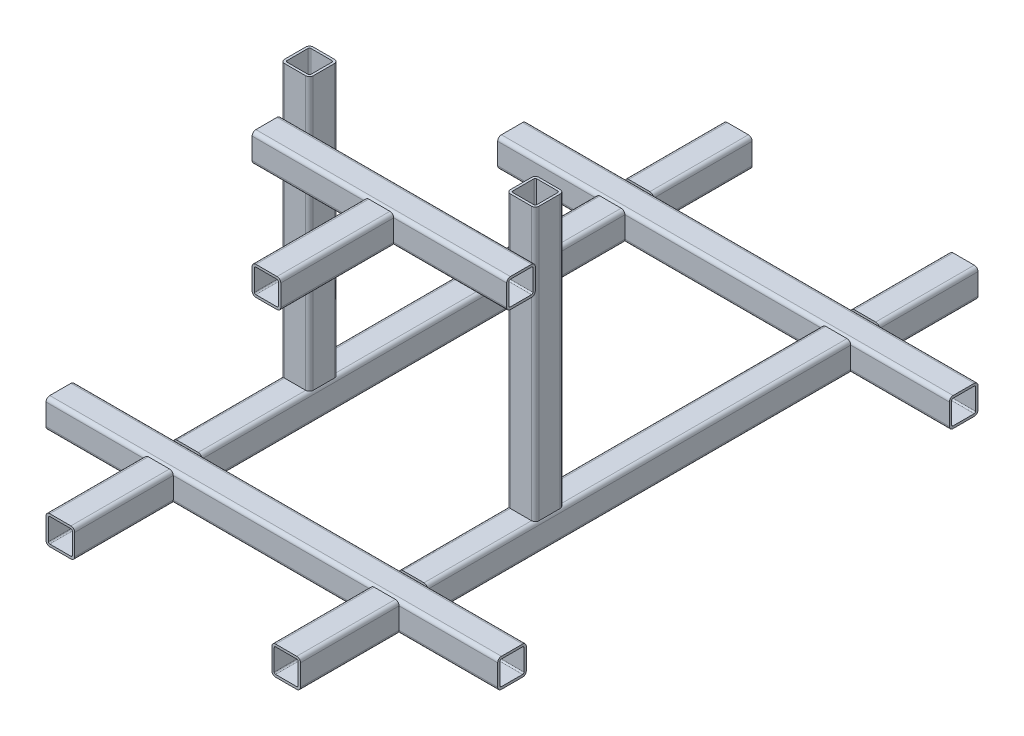
SolidWorks part; units mm, degrees
ref_plane "Front Plane" through (0, 0, 0) normal (0, 0, 1) x (1, 0, 0)
ref_plane "Top Plane" through (0, 0, 0) normal (0, 1, 0) x (1, 0, 0)
ref_plane "Right Plane" through (0, 0, 0) normal (1, 0, 0) x (0, 0, -1)
ref_plane "Bottom Face" through (0, 0, 0) normal (0, 1, 0) x (1, 0, 0)
ref_plane "Top Face" through (0, 38.1, 0) normal (0, 1, 0) x (1, 0, 0)
ref_plane "Mid Plane" through (0, 19.05, 0) normal (0, 1, 0) x (1, 0, 0)
ref_plane "Front Face" through (0, 0, 450) normal (0, 0, 1) x (1, 0, 0)
ref_plane "Back Face" through (0, 0, -450) normal (0, 0, 1) x (1, 0, 0)
ref_plane "Left Face" through (300, 0, 0) normal (1, 0, 0) x (0, 0, -1)
ref_plane "Right Face" through (-300, 0, 0) normal (1, 0, 0) x (0, 0, -1)
ref_plane "Divider Plane" through (0, 0, 100) normal (0, 0, 1) x (1, 0, 0)
ref_plane "Max Height Plane" through (0, 400, 0) normal (0, 1, 0) x (1, 0, 0)
ref_plane "Electronics Box Plane" through (0, 338.1, 0) normal (0, 1, 0) x (1, 0, 0)
sketch "Sketch2" plane through (300, 0, 0) normal (1, 0, 0) x (0, 0, -1)
  line L0 (275, 38.1) -> (-275, 38.1) construction
  line L5 (275, 0) -> (-275, 0) construction
  line L6 (0, 20.955) -> (0, -20.955) construction
  line L7 (-314.05, 38.1) -> (-285.95, 38.1)
  line L8 (-280.95, 33.1) -> (-280.95, 5)
  line L9 (-315.875, 33.1) -> (-315.875, 5)
  line L10 (-314.05, 3.175) -> (-285.95, 3.175)
  line L11 (-285.95, 0) -> (-314.05, 0)
  line L12 (-319.05, 5) -> (-319.05, 33.1)
  line L13 (-300, 38.1) -> (-300, 0) construction
  line L14 (-319.05, 19.05) -> (-280.95, 19.05) construction
  line L15 (-284.125, 5) -> (-284.125, 33.1)
  line L16 (-285.95, 34.925) -> (-314.05, 34.925)
  line L17 (-300, 34.925) -> (-300, 3.175) construction
  line L18 (-315.875, 19.05) -> (-284.125, 19.05) construction
  arc A0 (-285.95, 38.1) -> (-280.95, 33.1) centre (-285.95, 33.1) cw
  arc A1 (-280.95, 5) -> (-285.95, 0) centre (-285.95, 5) cw
  arc A2 (-314.05, 0) -> (-319.05, 5) centre (-314.05, 5) cw
  arc A3 (-319.05, 33.1) -> (-314.05, 38.1) centre (-314.05, 33.1) cw
  arc A4 (-315.875, 5) -> (-314.05, 3.175) centre (-314.05, 5) ccw
  arc A5 (-285.95, 3.175) -> (-284.125, 5) centre (-285.95, 5) ccw
  arc A6 (-284.125, 33.1) -> (-285.95, 34.925) centre (-285.95, 33.1) ccw
  arc A7 (-314.05, 34.925) -> (-315.875, 33.1) centre (-314.05, 33.1) ccw
  point P20 (-300, 19.05)
  point P39 (-300, 19.05)
  dimension "D1" = 5
  dimension "D2" = 300
  dimension "D3" = 3.175
extrude "Front Cross-Car Member" add sketch "Sketch2" against normal up to surface (600 mm away) up to plane "Right Face"
sketch "Sketch5" plane through (300, 0, 0) normal (1, 0, 0) x (0, 0, -1)
  line L0 (285.95, 38.1) -> (314.05, 38.1)
  line L1 (319.05, 33.1) -> (319.05, 5)
  line L2 (314.05, 0) -> (285.95, 0)
  line L3 (280.95, 5) -> (280.95, 33.1)
  line L4 (300, 38.1) -> (300, 0) construction
  line L5 (280.95, 19.05) -> (319.05, 19.05) construction
  line L6 (285.95, 34.925) -> (314.05, 34.925)
  line L7 (315.875, 33.1) -> (315.875, 5)
  line L8 (314.05, 3.175) -> (285.95, 3.175)
  line L9 (284.125, 5) -> (284.125, 33.1)
  line L10 (300, 34.925) -> (300, 3.175) construction
  line L11 (284.125, 19.05) -> (315.875, 19.05) construction
  line L12 (275, 0) -> (-275, 0) construction
  line L14 (275, 38.1) -> (-275, 38.1) construction
  line L15 (0, 20.955) -> (0, -20.955) construction
  arc A0 (314.05, 38.1) -> (319.05, 33.1) centre (314.05, 33.1) cw
  arc A1 (319.05, 5) -> (314.05, 0) centre (314.05, 5) cw
  arc A2 (285.95, 0) -> (280.95, 5) centre (285.95, 5) cw
  arc A3 (280.95, 33.1) -> (285.95, 38.1) centre (285.95, 33.1) cw
  arc A4 (314.05, 34.925) -> (315.875, 33.1) centre (314.05, 33.1) cw
  arc A5 (315.875, 5) -> (314.05, 3.175) centre (314.05, 5) cw
  arc A6 (285.95, 3.175) -> (284.125, 5) centre (285.95, 5) cw
  arc A7 (284.125, 33.1) -> (285.95, 34.925) centre (285.95, 33.1) cw
  point P32 (300, 19.05)
  point P33 (300, 19.05)
  point P38 (-188.7665, 32.0373)
  dimension "D2" = 5
  dimension "D1" = 3.175
  dimension "D3" = 300
extrude "Back Cross-Car Member" add sketch "Sketch5" against normal up to surface (600 mm away) separate body up to plane "Right Face"
sketch "Sketch6" plane through (0, 0, -450) normal (0, 0, 1) x (1, 0, 0)
  line L0 (135.95, 38.1) -> (164.05, 38.1)
  line L1 (169.05, 33.1) -> (169.05, 5)
  line L2 (134.125, 33.1) -> (134.125, 5)
  line L3 (135.95, 3.175) -> (164.05, 3.175)
  line L4 (164.05, 0) -> (135.95, 0)
  line L5 (130.95, 5) -> (130.95, 33.1)
  line L6 (150, 38.1) -> (150, 0) construction
  line L7 (130.95, 19.05) -> (169.05, 19.05) construction
  line L8 (165.875, 5) -> (165.875, 33.1)
  line L9 (164.05, 34.925) -> (135.95, 34.925)
  line L10 (150, 34.925) -> (150, 3.175) construction
  line L11 (134.125, 19.05) -> (165.875, 19.05) construction
  line L12 (275, 38.1) -> (-275, 38.1) construction
  line L13 (275, 0) -> (-275, 0) construction
  line L14 (0, -20.955) -> (0, 20.955) construction
  arc A0 (164.05, 38.1) -> (169.05, 33.1) centre (164.05, 33.1) cw
  arc A1 (169.05, 5) -> (164.05, 0) centre (164.05, 5) cw
  arc A2 (135.95, 0) -> (130.95, 5) centre (135.95, 5) cw
  arc A3 (130.95, 33.1) -> (135.95, 38.1) centre (135.95, 33.1) cw
  arc A4 (134.125, 5) -> (135.95, 3.175) centre (135.95, 5) ccw
  arc A5 (164.05, 3.175) -> (165.875, 5) centre (164.05, 5) ccw
  arc A6 (165.875, 33.1) -> (164.05, 34.925) centre (164.05, 33.1) ccw
  arc A7 (135.95, 34.925) -> (134.125, 33.1) centre (135.95, 33.1) ccw
  point P16 (150, 19.05)
  point P33 (150, 19.05)
  dimension "D1" = 5
  dimension "D2" = 3.175
  dimension "D3" = 150
extrude "Back Left Along-Car Member" add sketch "Sketch6" along normal blind 130.95
extrude "Middle Left Along-Car Member" add sketch "Sketch6<2>" along normal blind 561.9 from offset 169.05
sketch "Sketch6<2>" plane through (0, 0, -450) normal (0, 0, 1) x (1, 0, 0) same geometry as "Sketch6"
extrude "Front Left Along-Car Member" add sketch "Sketch6<3>" along normal blind 130.95 from offset 769.05
sketch "Sketch6<3>" plane through (0, 0, -450) normal (0, 0, 1) x (1, 0, 0) same geometry as "Sketch6"
sketch "Sketch7" plane through (0, 0, -450) normal (0, 0, 1) x (1, 0, 0)
  line L0 (-164.05, 38.1) -> (-135.95, 38.1)
  line L1 (-130.95, 33.1) -> (-130.95, 5)
  line L2 (-165.875, 33.1) -> (-165.875, 5)
  line L3 (-164.05, 3.175) -> (-135.95, 3.175)
  line L4 (-135.95, 0) -> (-164.05, 0)
  line L5 (-169.05, 5) -> (-169.05, 33.1)
  line L6 (-150, 38.1) -> (-150, 0) construction
  line L7 (-169.05, 19.05) -> (-130.95, 19.05) construction
  line L8 (-134.125, 5) -> (-134.125, 33.1)
  line L9 (-135.95, 34.925) -> (-164.05, 34.925)
  line L10 (-150, 34.925) -> (-150, 3.175) construction
  line L11 (-165.875, 19.05) -> (-134.125, 19.05) construction
  line L12 (275, 38.1) -> (-275, 38.1) construction
  line L13 (275, 0) -> (-275, 0) construction
  line L14 (0, -20.955) -> (0, 20.955) construction
  arc A0 (-135.95, 38.1) -> (-130.95, 33.1) centre (-135.95, 33.1) cw
  arc A1 (-130.95, 5) -> (-135.95, 0) centre (-135.95, 5) cw
  arc A2 (-164.05, 0) -> (-169.05, 5) centre (-164.05, 5) cw
  arc A3 (-169.05, 33.1) -> (-164.05, 38.1) centre (-164.05, 33.1) cw
  arc A4 (-165.875, 5) -> (-164.05, 3.175) centre (-164.05, 5) ccw
  arc A5 (-135.95, 3.175) -> (-134.125, 5) centre (-135.95, 5) ccw
  arc A6 (-134.125, 33.1) -> (-135.95, 34.925) centre (-135.95, 33.1) ccw
  arc A7 (-164.05, 34.925) -> (-165.875, 33.1) centre (-164.05, 33.1) ccw
  point P16 (-150, 19.05)
  point P33 (-150, 19.05)
  dimension "D1" = 5
  dimension "D2" = 3.175
  dimension "D3" = 150
extrude "Back Right Along-Car Member" add sketch "Sketch7" along normal blind 130.95
extrude "Middle Right Along-Car Member" add sketch "Sketch7<2>" along normal blind 561.9 from offset 169.05
sketch "Sketch7<2>" plane through (0, 0, -450) normal (0, 0, 1) x (1, 0, 0) same geometry as "Sketch7"
extrude "Front Right Along-Car Member" add sketch "Sketch7<3>" along normal blind 130.95 from offset 769.05
sketch "Sketch7<3>" plane through (0, 0, -450) normal (0, 0, 1) x (1, 0, 0) same geometry as "Sketch7"
sketch "Sketch8" plane through (0, 38.1, 0) normal (0, 1, 0) x (1, 0, 0)
  line L0 (-164.05, -100) -> (-135.95, -100)
  line L1 (-130.95, -105) -> (-130.95, -133.1)
  line L2 (-165.875, -105) -> (-165.875, -133.1)
  line L3 (-164.05, -134.925) -> (-135.95, -134.925)
  line L4 (-135.95, -138.1) -> (-164.05, -138.1)
  line L5 (-169.05, -133.1) -> (-169.05, -105)
  line L6 (-150, -100) -> (-150, -138.1) construction
  line L7 (-169.05, -119.05) -> (-130.95, -119.05) construction
  line L8 (-134.125, -133.1) -> (-134.125, -105)
  line L9 (-135.95, -103.175) -> (-164.05, -103.175)
  line L10 (-150, -103.175) -> (-150, -134.925) construction
  line L11 (-165.875, -119.05) -> (-134.125, -119.05) construction
  line L12 (-20.955, -100) -> (20.955, -100) construction
  line L13 (0, -20.955) -> (0, 20.955) construction
  arc A0 (-135.95, -100) -> (-130.95, -105) centre (-135.95, -105) cw
  arc A1 (-130.95, -133.1) -> (-135.95, -138.1) centre (-135.95, -133.1) cw
  arc A2 (-164.05, -138.1) -> (-169.05, -133.1) centre (-164.05, -133.1) cw
  arc A3 (-169.05, -105) -> (-164.05, -100) centre (-164.05, -105) cw
  arc A4 (-165.875, -133.1) -> (-164.05, -134.925) centre (-164.05, -133.1) ccw
  arc A5 (-135.95, -134.925) -> (-134.125, -133.1) centre (-135.95, -133.1) ccw
  arc A6 (-134.125, -105) -> (-135.95, -103.175) centre (-135.95, -105) ccw
  arc A7 (-164.05, -103.175) -> (-165.875, -105) centre (-164.05, -105) ccw
  point P16 (-150, -119.05)
  point P33 (-150, -119.05)
  dimension "D1" = 5
  dimension "D2" = 3.175
  dimension "D3" = 38.1
  dimension "D4" = 150
extrude "Right Vertical Member" add sketch "Sketch8" along normal up to surface (361.9 mm away) up to plane "Max Height Plane"
sketch "Sketch10" plane through (0, 38.1, 0) normal (0, 1, 0) x (1, 0, 0)
  line L0 (135.95, -100) -> (164.05, -100)
  line L1 (169.05, -105) -> (169.05, -133.1)
  line L2 (134.125, -105) -> (134.125, -133.1)
  line L3 (135.95, -134.925) -> (164.05, -134.925)
  line L4 (164.05, -138.1) -> (135.95, -138.1)
  line L5 (130.95, -133.1) -> (130.95, -105)
  line L6 (150, -100) -> (150, -138.1) construction
  line L7 (130.95, -119.05) -> (169.05, -119.05) construction
  line L8 (165.875, -133.1) -> (165.875, -105)
  line L9 (164.05, -103.175) -> (135.95, -103.175)
  line L10 (150, -103.175) -> (150, -134.925) construction
  line L11 (134.125, -119.05) -> (165.875, -119.05) construction
  line L12 (-165, -100) -> (165, -100) construction
  line L13 (0, -165) -> (0, 165) construction
  arc A0 (164.05, -100) -> (169.05, -105) centre (164.05, -105) cw
  arc A1 (169.05, -133.1) -> (164.05, -138.1) centre (164.05, -133.1) cw
  arc A2 (135.95, -138.1) -> (130.95, -133.1) centre (135.95, -133.1) cw
  arc A3 (130.95, -105) -> (135.95, -100) centre (135.95, -105) cw
  arc A4 (134.125, -133.1) -> (135.95, -134.925) centre (135.95, -133.1) ccw
  arc A5 (164.05, -134.925) -> (165.875, -133.1) centre (164.05, -133.1) ccw
  arc A6 (165.875, -105) -> (164.05, -103.175) centre (164.05, -105) ccw
  arc A7 (135.95, -103.175) -> (134.125, -105) centre (135.95, -105) ccw
  point P16 (150, -119.05)
  point P33 (150, -119.05)
  dimension "D1" = 5
  dimension "D2" = 3.175
  dimension "D3" = 38.1
  dimension "D4" = 150
extrude "Left Vertical Member" add sketch "Sketch10" along normal up to surface (361.9 mm away) up to plane "Max Height Plane"
sketch "Sketch11" plane through (300, 0, 0) normal (1, 0, 0) x (0, 0, -1)
  line L0 (-171.2, 338.1) -> (-143.1, 338.1)
  line L1 (-138.1, 333.1) -> (-138.1, 305)
  line L2 (-173.025, 333.1) -> (-173.025, 305)
  line L3 (-171.2, 303.175) -> (-143.1, 303.175)
  line L4 (-143.1, 300) -> (-171.2, 300)
  line L5 (-176.2, 305) -> (-176.2, 333.1)
  line L6 (-157.15, 338.1) -> (-157.15, 300) construction
  line L7 (-176.2, 319.05) -> (-138.1, 319.05) construction
  line L8 (-141.275, 305) -> (-141.275, 333.1)
  line L9 (-143.1, 334.925) -> (-171.2, 334.925)
  line L10 (-157.15, 334.925) -> (-157.15, 303.175) construction
  line L11 (-173.025, 319.05) -> (-141.275, 319.05) construction
  line L12 (-100, 165) -> (-100, -165) construction
  line L13 (330, 338.1) -> (-330, 338.1) construction
  arc A0 (-143.1, 338.1) -> (-138.1, 333.1) centre (-143.1, 333.1) cw
  arc A1 (-138.1, 305) -> (-143.1, 300) centre (-143.1, 305) cw
  arc A2 (-171.2, 300) -> (-176.2, 305) centre (-171.2, 305) cw
  arc A3 (-176.2, 333.1) -> (-171.2, 338.1) centre (-171.2, 333.1) cw
  arc A4 (-173.025, 305) -> (-171.2, 303.175) centre (-171.2, 305) ccw
  arc A5 (-143.1, 303.175) -> (-141.275, 305) centre (-143.1, 305) ccw
  arc A6 (-141.275, 333.1) -> (-143.1, 334.925) centre (-143.1, 333.1) ccw
  arc A7 (-171.2, 334.925) -> (-173.025, 333.1) centre (-171.2, 333.1) ccw
  point P16 (-157.15, 319.05)
  point P33 (-157.15, 319.05)
  dimension "D1" = 5
  dimension "D2" = 3.175
  dimension "D3" = 38.1
  dimension "D4" = 38.1
extrude "Upper Cross-Car Member" add sketch "Sketch11" against normal blind 338.1 from offset 130.95 offset against normal yes
sketch "Sketch12" plane through (0, 0, 100) normal (0, 0, 1) x (1, 0, 0)
  line L0 (-14.05, 338.1) -> (14.05, 338.1)
  line L1 (19.05, 333.1) -> (19.05, 305)
  line L2 (-15.875, 333.1) -> (-15.875, 305)
  line L3 (-14.05, 303.175) -> (14.05, 303.175)
  line L4 (14.05, 300) -> (-14.05, 300)
  line L5 (-19.05, 305) -> (-19.05, 333.1)
  line L6 (0, 338.1) -> (0, 300) construction
  line L7 (-19.05, 319.05) -> (19.05, 319.05) construction
  line L8 (15.875, 305) -> (15.875, 333.1)
  line L9 (14.05, 334.925) -> (-14.05, 334.925)
  line L10 (0, 334.925) -> (0, 303.175) construction
  line L11 (-15.875, 319.05) -> (15.875, 319.05) construction
  line L12 (330, 338.1) -> (-330, 338.1) construction
  line L13 (0, -165) -> (0, 165) construction
  arc A0 (14.05, 338.1) -> (19.05, 333.1) centre (14.05, 333.1) cw
  arc A1 (19.05, 305) -> (14.05, 300) centre (14.05, 305) cw
  arc A2 (-14.05, 300) -> (-19.05, 305) centre (-14.05, 305) cw
  arc A3 (-19.05, 333.1) -> (-14.05, 338.1) centre (-14.05, 333.1) cw
  arc A4 (-15.875, 305) -> (-14.05, 303.175) centre (-14.05, 305) ccw
  arc A5 (14.05, 303.175) -> (15.875, 305) centre (14.05, 305) ccw
  arc A6 (15.875, 333.1) -> (14.05, 334.925) centre (14.05, 333.1) ccw
  arc A7 (-14.05, 334.925) -> (-15.875, 333.1) centre (-14.05, 333.1) ccw
  point P16 (0, 319.05)
  point P33 (0, 319.05)
  dimension "D1" = 5
  dimension "D2" = 3.175
  dimension "D3" = 38.1
extrude "Boss-Extrude12" add sketch "Sketch12" along normal blind 150 from offset 76.2
equation "\"frameLength\" = 900mm"
equation "\"frameWidth\" = 600mm"
equation "\"memberDistWidth\"= 300mm"
equation "\"memberDistLength\" = 600mm"
equation "\"tubeStockHeight\"= 1.5 * 25.4mm"
equation "\"tubeStockWallThickness\"= 0.125 * 25.4mm"
equation "\"D1@Front Face\" = \"frameLength\" / 2"
equation "\"D1@Back Face\" = \"frameLength\" / 2"
equation "\"D1@Left Face\"=\"frameWidth\"/2"
equation "\"D1@Right Face\" = \"frameWidth\" / 2"
equation "\"D1@Top Face\"=\"tubeStockHeight\""
equation "\"D2@Sketch2\"=\"memberDistLength\"/2"
equation "\"D3@Sketch2\"=\"tubeStockWallThickness\""
equation "\"D1@Sketch5\"=\"tubeStockWallThickness\""
equation "\"D3@Sketch5\"=\"memberDistLength\"/2"
equation "\"D3@Sketch6\"=\"memberDistWidth\"/2"
equation "\"D1@Back Left Along-Car Member\" =  ( \"frameLength\" - \"memberDistLength\" - \"tubeStockHeight\" )  / 2"
equation "\"D19@Middle Left Along-Car Member\" =  ( \"frameLength\" - \"memberDistLength\" + \"tubeStockHeight\" )  / 2"
equation "\"D1@Middle Left Along-Car Member\" = \"memberDistLength\" - \"tubeStockHeight\""
equation "\"D19@Front Left Along-Car Member\" =  ( \"frameLength\" - \"memberDistLength\" )  / 2 + \"memberDistLength\" + \"tubeStockHeight\" / 2"
equation "\"D1@Front Left Along-Car Member\" =  ( \"frameLength\" - \"memberDistLength\" - \"tubeStockHeight\" )  / 2"
equation "\"D3@Sketch7\"=\"memberDistWidth\"/2"
equation "\"D1@Back Right Along-Car Member\" =  ( \"frameLength\" - \"memberDistLength\" - \"tubeStockHeight\" )  / 2"
equation "\"D19@Middle Right Along-Car Member\" =  ( \"frameLength\" - \"memberDistLength\" + \"tubeStockHeight\" )  / 2"
equation "\"D1@Middle Right Along-Car Member\" = \"memberDistLength\" - \"tubeStockHeight\""
equation "\"D19@Front Right Along-Car Member\" =  ( \"frameLength\" - \"memberDistLength\" )  / 2 + \"memberDistLength\" + \"tubeStockHeight\" / 2"
equation "\"D1@Front Right Along-Car Member\" =  ( \"frameLength\" - \"memberDistLength\" - \"tubeStockHeight\" )  / 2"
equation "\"dividerPlaneOffset\"= 100mm"
equation "\"D1@Divider Plane\" = \"dividerPlaneOffset\""
equation "\"D3@Sketch8\"=\"tubeStockHeight\""
equation "\"D4@Sketch8\"=\"memberDistWidth\"/2"
equation "\"frameHeight\" = 400mm"
equation "\"D1@Max Height Plane\" = \"frameHeight\""
equation "\"D4@Sketch10\"=\"memberDistWidth\"/2"
equation "\"electronicsBoxPlaneHeight\" = 300mm"
equation "\"D1@Electronics Box Plane\" = \"electronicsBoxPlaneHeight\""
equation "\"D4@Sketch11\"=\"tubeStockHeight\""
equation "\"D19@Upper Cross-Car Member\" =  ( \"frameWidth\" - \"memberDistWidth\" - \"tubeStockHeight\" )  / 2"
equation "\"D1@Upper Cross-Car Member\" = \"memberDistWidth\" + \"tubeStockHeight\""
equation "\"D19@Boss-Extrude12\"=\"tubeStockHeight\"*2"
